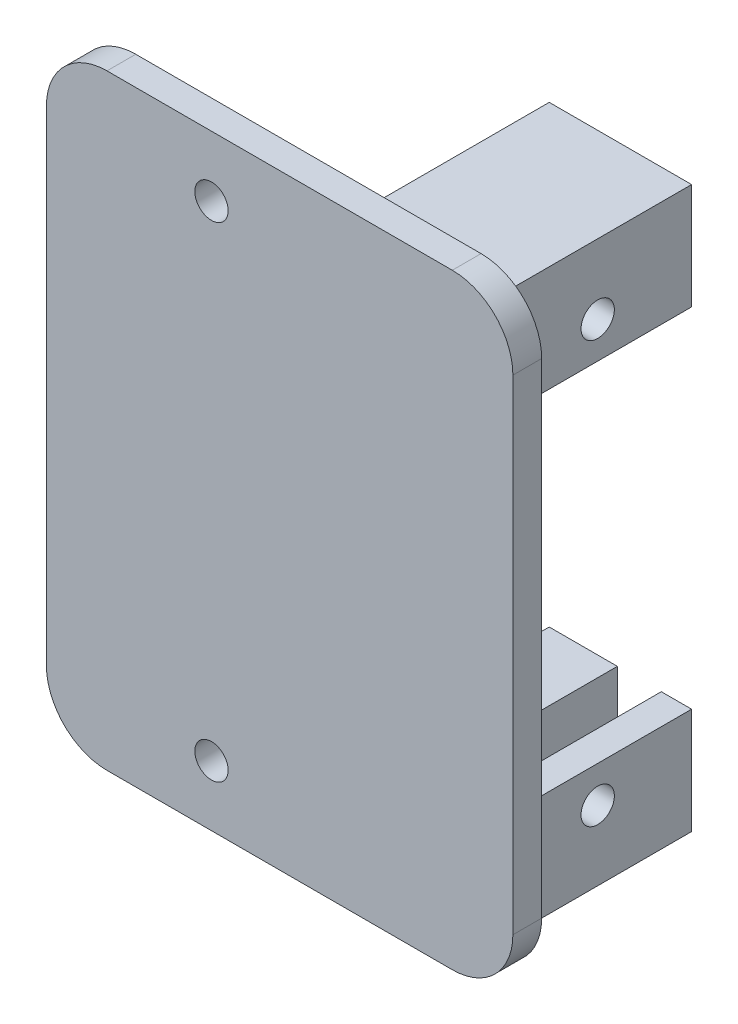
SolidWorks part; units mm, degrees
ref_plane "Płaszczyzna przednia" through (0, 0, 0) normal (0, 0, 1) x (1, 0, 0)
ref_plane "Płaszczyzna górna" through (0, 0, 0) normal (0, 1, 0) x (1, 0, 0)
ref_plane "Płaszczyzna prawa" through (0, 0, 0) normal (1, 0, 0) x (0, 0, -1)
sketch "Szkic1" plane through (0, 0, 0) normal (0, 0, 1) x (1, 0, 0)
  line L0 (-12.9, 20) -> (12.9, 20)
  line L1 (-16.9, 0) -> (16.9, 0) construction
  line L2 (16.9, -16) -> (16.9, 16)
  line L3 (-12.9, -20) -> (12.9, -20)
  line L5 (-16.9, -16) -> (-16.9, 16)
  line L8 (0, 20) -> (0, -20) construction
  arc A0 (12.9, 20) -> (16.9, 16) centre (12.9, 16) cw
  arc A1 (-12.9, -20) -> (-16.9, -16) centre (-12.9, -16) cw
  arc A2 (-12.9, 20) -> (-16.9, 16) centre (-12.9, 16) ccw
  arc A3 (12.9, -20) -> (16.9, -16) centre (12.9, -16) ccw
  point P0 (0, 0)
  point P10 (0, 0)
  dimension "D3" = 4
  dimension "D1" = 20
  dimension "D2" = 16.9
extrude "Dodanie-wyciągnięcie1" add sketch "Szkic1" along normal blind 1.9 contours A1 A0 L5 | L8 A0 region at (0, 0, 0)
sketch "Szkic3" plane through (0, 0, 0) normal (0, 0, -1) x (-1, 0, 0)
  line L11 (-16.9, 0) -> (16.9, 0) construction
  line L12 (-9.4, -16.5) -> (-9.4, -11.5)
  line L13 (-6.5, -16.5) -> (-9.4, -16.5)
  line L39 (-16.9, -16) -> (-16.9, 16) construction
  line L40 (16.9, -16) -> (16.9, 16) construction
  line L41 (-9.4, 11.5) -> (-11.4, 11.5)
  line L42 (-11.4, 11.5) -> (-11.4, 18.5)
  line L43 (-11.4, 18.5) -> (-2, 18.5)
  line L44 (-2, 18.5) -> (-2, 11.5)
  line L45 (-2, 11.5) -> (-6.5, 11.5)
  line L46 (-6.5, 11.5) -> (-6.5, 16.5)
  line L47 (-6.5, 16.5) -> (-9.4, 16.5)
  line L48 (-9.4, 16.5) -> (-9.4, 11.5)
  line L49 (-6.5, -11.5) -> (-6.5, -16.5)
  line L50 (-2, -11.5) -> (-6.5, -11.5)
  line L51 (-2, -18.5) -> (-2, -11.5)
  line L52 (-11.4, -18.5) -> (-2, -18.5)
  line L53 (-11.4, -11.5) -> (-11.4, -18.5)
  line L54 (-9.4, -11.5) -> (-11.4, -11.5)
  point P58 (-10.4, 11.5)
  dimension "D7" = 2
  dimension "D8" = 4.5
  dimension "D9" = 2
  dimension "D10" = 5
  dimension "D11" = 23
  dimension "D12" = 5.5
  dimension "D13" = 2.9
extrude "Dodanie-wyciągnięcie3" add sketch "Szkic3" along normal blind 12.4 contours L48 L47 L46 L45 L44 L43 L42 L41 | L12 L54 L53 L52 L51 L50 L49 L13 region at (6.3467, -15.2827, 0) region at (6.3467, 15.2827, 0)
sketch "Esquisse4" plane through (-16.9, 0, 0) normal (-1, 0, 0) x (0, 0, 1)
  line L0 (-3.5791, 8.3914) -> (0, 5.4422)
  line L1 (0, -16) -> (0, 16) construction
  line L2 (-8.9209, 1.9086) -> (0, -5.4422)
  line L3 (0, 5.4422) -> (0, -5.4422)
  line L14 (1.9, -20) -> (0, -20) construction
  line L15 (1.9, -16) -> (1.9, 16) construction
  circle A3 centre (-6.25, 5.15) radius 2.2
  arc A4 (-3.5791, 8.3914) -> (-8.9209, 1.9086) centre (-6.25, 5.15) ccw
  point P0 (0, 0)
  line M5 (0, 16) -> (0, -16)
  dimension "D5" = 4.4
  dimension "D6" = 2
  dimension "D7" = 25.15
  dimension "D8" = 8.15
extrude "Boss.-Extru.2" add sketch "Esquisse4" against normal blind 2 contours A4 A3 M5 region at (-16.9, 2.8424, -4.2442)
sketch "Esquisse5" plane through (0, 0, 0) normal (0, 0, -1) x (-1, 0, 0)
  line L0 (0, 0) -> (14.9, 0) construction
  line L1 (-2, 18.5) -> (-2, 11.5) construction
  line L8 (14.9, 5.4422) -> (16.9, 5.4422)
  line L9 (16.9, 5.4422) -> (16.9, 16)
  line L10 (12.9, 20) -> (-12.9, 20)
  line L11 (-16.9, 16) -> (-16.9, -16)
  line L12 (-12.9, -20) -> (12.9, -20)
  line L13 (16.9, -16) -> (16.9, -5.4422)
  line L14 (16.9, -5.4422) -> (14.9, -5.4422)
  line L15 (14.9, -5.4422) -> (14.9, 5.4422)
  line L16 (14.9, 5.4422) -> (16.9, 5.4422)
  line L17 (16.9, 5.4422) -> (16.9, 16)
  line L18 (12.9, 20) -> (-12.9, 20)
  line L19 (-16.9, 16) -> (-16.9, -16)
  line L20 (-12.9, -20) -> (12.9, -20)
  line L21 (16.9, -16) -> (16.9, -5.4422)
  line L22 (16.9, -5.4422) -> (14.9, -5.4422)
  line L23 (14.9, -5.4422) -> (14.9, 5.4422)
  circle A0 centre (6, 16) radius 1.1
  circle A1 centre (6, -16) radius 1.1
  arc A4 (16.9, 16) -> (12.9, 20) centre (12.9, 16) ccw
  arc A5 (-12.9, 20) -> (-16.9, 16) centre (-12.9, 16) ccw
  arc A6 (-16.9, -16) -> (-12.9, -20) centre (-12.9, -16) ccw
  arc A7 (12.9, -20) -> (16.9, -16) centre (12.9, -16) ccw
  arc A8 (16.9, 16) -> (12.9, 20) centre (12.9, 16) ccw
  arc A9 (-12.9, 20) -> (-16.9, 16) centre (-12.9, 16) ccw
  arc A10 (-16.9, -16) -> (-12.9, -20) centre (-12.9, -16) ccw
  arc A11 (12.9, -20) -> (16.9, -16) centre (12.9, -16) ccw
  dimension "D3" = 2.2
  dimension "D2" = 4
  dimension "D4" = 8
  dimension "D1" = 0
extrude "Enlèv. mat.-Extru.2" cut sketch "Esquisse5" against normal through all contours A0 | A1 region at (-6, 16, 0) region at (-6, -16, 0)
sketch "Esquisse6" plane through (11.4, 0, 0) normal (1, 0, 0) x (0, 0, -1)
  line L0 (0, 18.5) -> (0, 11.5) construction
  line L1 (0, 11.5) -> (12.4, 11.5) construction
  line L2 (12.4, 11.5) -> (12.4, 18.5) construction
  line L3 (12.4, 18.5) -> (0, 18.5) construction
  line L4 (0, -11.5) -> (0, -18.5) construction
  line L5 (0, -18.5) -> (12.4, -18.5) construction
  line L6 (12.4, -18.5) -> (12.4, -11.5) construction
  line L7 (12.4, -11.5) -> (0, -11.5) construction
  line L8 (0, 18.5) -> (0, 11.5)
  line L9 (0, 11.5) -> (12.4, 11.5)
  line L10 (12.4, 11.5) -> (12.4, 18.5)
  line L11 (12.4, 18.5) -> (0, 18.5)
  line L12 (0, -11.5) -> (0, -18.5)
  line L13 (0, -18.5) -> (12.4, -18.5)
  line L14 (12.4, -18.5) -> (12.4, -11.5)
  line L15 (12.4, -11.5) -> (0, -11.5)
  line L16 (0, 0) -> (-1.9, 0) construction
  line L17 (-1.9, -16) -> (-1.9, 16) construction
  circle A0 centre (6.2, 13.9) radius 1.1
  circle A1 centre (6.2, -13.9) radius 1.1
  point P18 (6.2, 11.5)
  dimension "D1" = 2.2
  dimension "D2" = 27.8
extrude "Enlèv. mat.-Extru.4" cut sketch "Esquisse6" against normal up to surface (9.4 mm away) contours A0 | A1 region at (11.4, 13.9, -6.2) region at (11.4, -13.9, -6.2) up to face at (2, 15, -6.2)
sketch "Esquisse7" plane through (2, 0, 0) normal (-1, 0, 0) x (0, 0, 1)
  circle A0 centre (-6.2, -13.9) radius 1.1 construction
  circle A1 centre (-6.2, 13.9) radius 1.1 construction
  circle A2 centre (-6.2, -13.9) radius 1.1
  circle A3 centre (-6.2, 13.9) radius 1.1
  circle A4 centre (-6.2, 13.9) radius 1.6
  circle A5 centre (-6.2, -13.9) radius 1.6
  dimension "D1" = 3.2
extrude "Enlèv. mat.-Extru.5" cut sketch "Esquisse7" against normal blind 2.2 contours A4 A3 | A3 | A5 A2 | A2 region at (2, -13.9, -6.2) region at (2, 13.9, -6.2) region at (2, 13.9, -7.7547) region at (2, -13.9, -7.7547)
sketch "Esquisse8" plane through (0, 0, 0) normal (0, 0, -1) x (-1, 0, 0)
  line L0 (-13.9, 16) -> (-13.9, -16)
  line L8 (14.9, 5.4422) -> (16.9, 5.4422)
  line L9 (16.9, 5.4422) -> (16.9, 16)
  line L10 (12.9, 20) -> (-12.9, 20)
  line L11 (-16.9, 16) -> (-16.9, -16)
  line L12 (-12.9, -20) -> (12.9, -20)
  line L13 (16.9, -16) -> (16.9, -5.4422)
  line L14 (16.9, -5.4422) -> (14.9, -5.4422)
  line L15 (14.9, -5.4422) -> (14.9, 5.4422)
  line L16 (14.9, 5.4422) -> (16.9, 5.4422)
  line L17 (16.9, 5.4422) -> (16.9, 16)
  line L18 (12.9, 20) -> (-12.9, 20)
  line L19 (-16.9, 16) -> (-16.9, -16)
  line L20 (-12.9, -20) -> (12.9, -20)
  line L21 (16.9, -16) -> (16.9, -5.4422)
  line L22 (16.9, -5.4422) -> (14.9, -5.4422)
  line L23 (14.9, -5.4422) -> (14.9, 5.4422)
  arc A0 (-9.9, 20) -> (-13.9, 16) centre (-9.9, 16) ccw
  arc A1 (-13.9, -16) -> (-9.9, -20) centre (-9.9, -16) ccw
  arc A4 (16.9, 16) -> (12.9, 20) centre (12.9, 16) ccw
  arc A5 (-12.9, 20) -> (-16.9, 16) centre (-12.9, 16) ccw
  arc A6 (-16.9, -16) -> (-12.9, -20) centre (-12.9, -16) ccw
  arc A7 (12.9, -20) -> (16.9, -16) centre (12.9, -16) ccw
  arc A8 (16.9, 16) -> (12.9, 20) centre (12.9, 16) ccw
  arc A9 (-12.9, 20) -> (-16.9, 16) centre (-12.9, 16) ccw
  arc A10 (-16.9, -16) -> (-12.9, -20) centre (-12.9, -16) ccw
  arc A11 (12.9, -20) -> (16.9, -16) centre (12.9, -16) ccw
  point P19 (0, 0)
  arc M17 (-12.9, 20) -> (-16.9, 16) centre (-12.9, 16) ccw
  line M18 (-16.9, 16) -> (-16.9, -16)
  arc M19 (-16.9, -16) -> (-12.9, -20) centre (-12.9, -16) ccw
  line M20 (-12.9, -20) -> (12.9, -20)
  dimension "D2" = 3
  dimension "D1" = 0
extrude "Enlèv. mat.-Extru.6" cut sketch "Esquisse8" against normal through all contours A1 L0 A0 L18 M17 M18 M19 M20 region at (15.2283, 0, 0)
